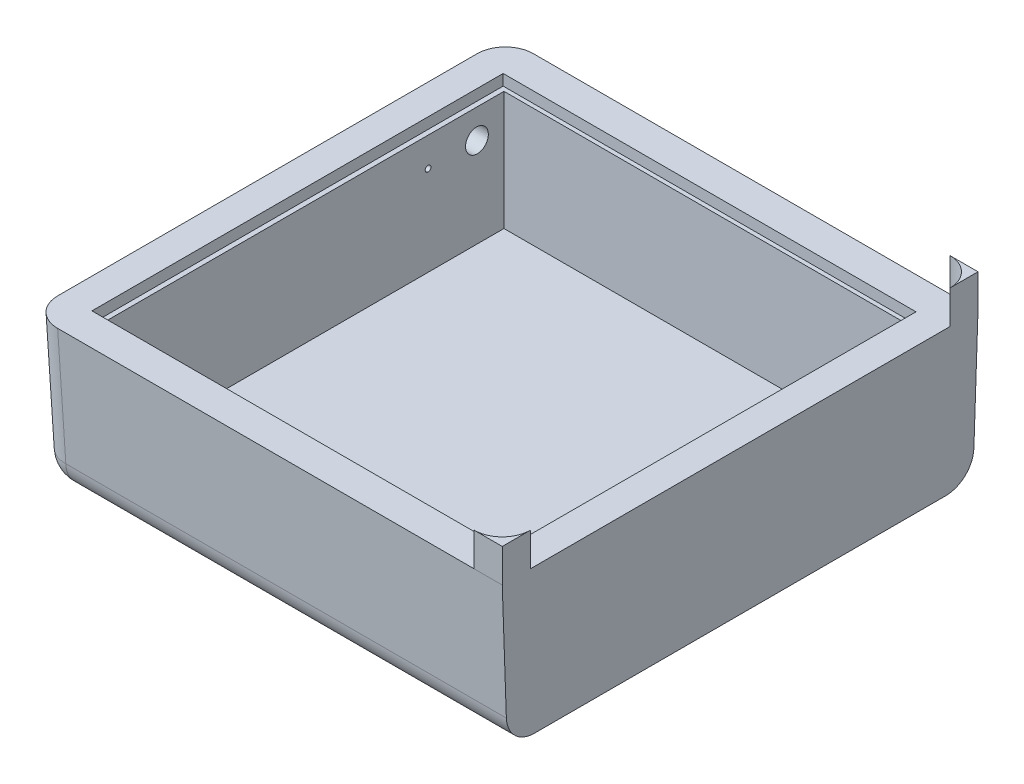
SolidWorks part; units mm, degrees
ref_plane "Front Plane" through (0, 0, 0) normal (0, 0, 1) x (1, 0, 0)
ref_plane "Top Plane" through (0, 0, 0) normal (0, 1, 0) x (1, 0, 0)
ref_plane "Right Plane" through (0, 0, 0) normal (1, 0, 0) x (0, 0, -1)
sketch "Sketch1" plane through (0, 0, 0) normal (0, 1, 0) x (1, 0, 0)
  line L1 (-145.25, -146.05) -> (149.75, -146.05)
  line L2 (-145.25, -146.05) -> (-145.25, 146.05)
  line L3 (-145.25, 146.05) -> (149.75, 146.05)
  line L4 (149.75, -146.05) -> (149.75, 146.05)
  point P0 (-145.25, 0)
  dimension "D1" = 145.25
  dimension "D3" = 292.1
  dimension "D5" = 295
extrude "Boss-Extrude1" add sketch "Sketch1" against normal blind 88.69 draft 2
sketch "Sketch3" plane through (0, 0, 0) normal (0, 1, 0) x (1, 0, 0)
  line L1 (-126.75, -126.25) -> (126.75, -126.25)
  line L4 (126.75, 126.25) -> (126.75, -126.25)
  line L9 (-126.75, 126.25) -> (-126.75, -126.25)
  line L183 (-126.75, 126.25) -> (126.75, 126.25)
  point P1 (-126.75, 0)
  dimension "D2" = 253.5
  dimension "D3" = 126.75
  dimension "D1" = 252.5
extrude "Cut-Extrude3" cut sketch "Sketch3" against normal blind 6.5 draft 2
sketch "Sketch5" plane through (0, -6.5, 0) normal (0, 1, 0) x (1, 0, 0)
  line L1 (-123.5, -123.5) -> (123.5, -123.5)
  line L2 (-123.5, -123.5) -> (-123.5, 123.5)
  line L3 (-123.5, 123.5) -> (123.5, 123.5)
  line L4 (123.5, -123.5) -> (123.5, 123.5)
  line L5 (-123.5, -123.5) -> (123.5, 123.5) construction
  line L6 (-123.5, 123.5) -> (123.5, -123.5) construction
  point P0 (0, 0)
  dimension "D1" = 247
extrude "Cut-Extrude4" cut sketch "Sketch5" against normal blind 70.5 draft 2
sketch "Sketch6" plane through (0, 0, 0) normal (0, 0, 1) x (1, 0, 0)
  line L0 (149.75, 0) -> (145, 0)
  line L1 (-145.25, 0) -> (149.75, 0) construction
  line L2 (145, 0) -> (145, -88.69)
  line L3 (-142.1529, -88.69) -> (146.6529, -88.69) construction
  line L4 (145, -88.69) -> (146.6529, -88.69)
  line L5 (146.6529, -88.69) -> (149.75, 0)
  dimension "D1" = 4.75
extrude "Cut-Extrude5" cut sketch "Sketch6" against normal through all both and the other way through all
fillet "Fillet2" radius 17.27 5 edges at (1.4236, -88.69, -142.9529) (-143.7014, -44.345, -144.5014) (-142.1529, -88.69, 0) (-143.7014, -44.345, 144.5014) (1.4236, -88.69, 142.9529)
sketch "Sketch7" plane through (0, 0, 0) normal (0, 1, 0) x (1, 0, 0)
  line L0 (-31.4885, 0) -> (69.7112, 0) construction
  line L1 (145, 146.05) -> (-127.9905, 146.05) construction
  line L2 (145, 146.05) -> (145, -146.05) construction
  line L3 (145, 128.78) -> (145, 146.05)
  line L4 (145, 146.05) -> (127.73, 146.05)
  line L5 (145, -146.05) -> (127.73, -146.05)
  line L6 (145, -128.78) -> (145, -146.05)
  arc A0 (127.73, 146.05) -> (145, 128.78) centre (127.73, 128.78) cw
  arc A1 (127.73, -146.05) -> (145, -128.78) centre (127.73, -128.78) ccw
  dimension "D1" = 17.27
extrude "Boss-Extrude2" add sketch "Sketch7" along normal blind 20.53
sketch "Sketch8" plane through (-145.0731, -5.0661, 0) normal (-0.9994, -0.0349, 0) x (0, 0, 1)
  line L0 (-128.7905, 5.0692) -> (128.7905, 5.0692) construction
  line L2 (-81, -22.2508) -> (-71.6, -22.2508)
  line L3 (-123.5, -10.8061) -> (-123.5, -2.186) construction
  line L4 (-82, -21.2508) -> (-82, -17.5508)
  line L5 (-81, -16.5508) -> (-71.6, -16.5508)
  line L6 (-70.6, -21.2508) -> (-70.6, -17.5508)
  line L7 (-82, -22.2508) -> (-70.6, -16.5508) construction
  line L8 (-82, -16.5508) -> (-70.6, -22.2508) construction
  circle A0 centre (-106.3, -19.4008) radius 7
  arc A1 (-71.6, -16.5508) -> (-70.6, -17.5508) centre (-71.6, -17.5508) cw
  arc A2 (-71.6, -22.2508) -> (-70.6, -21.2508) centre (-71.6, -21.2508) ccw
  arc A3 (-81, -22.2508) -> (-82, -21.2508) centre (-81, -21.2508) cw
  arc A4 (-82, -17.5508) -> (-81, -16.5508) centre (-81, -17.5508) cw
  point P4 (-76.3, -19.4008)
  point P23 (0, 0)
  dimension "D3" = 14
  dimension "D5" = 1
  dimension "D1" = 24.47
  dimension "D2" = 17.2
  dimension "D4" = 30
  dimension "D6" = 9.4
  dimension "D7" = 3.7
extrude "Cut-Extrude6" cut sketch "Sketch8" against normal up to next contours A0 region at (-144.396, -24.4551, -106.3)
extrude "Cut-Extrude7" cut sketch "Sketch8<3>" against normal blind 5 contours A4 L4 A3 L2 A2 L6 A1 L5 region at (-144.396, -24.4551, -76.3)
sketch "Sketch8<3>" plane through (-145.0731, -5.0661, 0) normal (-0.9994, -0.0349, 0) x (0, 0, 1) same geometry as "Sketch8"
sketch "Sketch9" plane through (-140.0761, -4.8916, 0) normal (-0.9994, -0.0349, 0) x (0, 0, 1)
  line L2 (-70.6, -21.2508) -> (-70.6, -17.5508) construction
  line L3 (-81, -22.2508) -> (-71.6, -22.2508) construction
  circle A0 centre (-76.3, -19.4008) radius 1.75
  point P2 (0, 0)
  point P3 (0, 0)
  point P5 (0, 0)
  point P8 (-70.6, -19.4008)
  point P10 (-76.3, -22.2508)
  dimension "D1" = 3.5
extrude "Cut-Extrude8" cut sketch "Sketch9" against normal up to next
